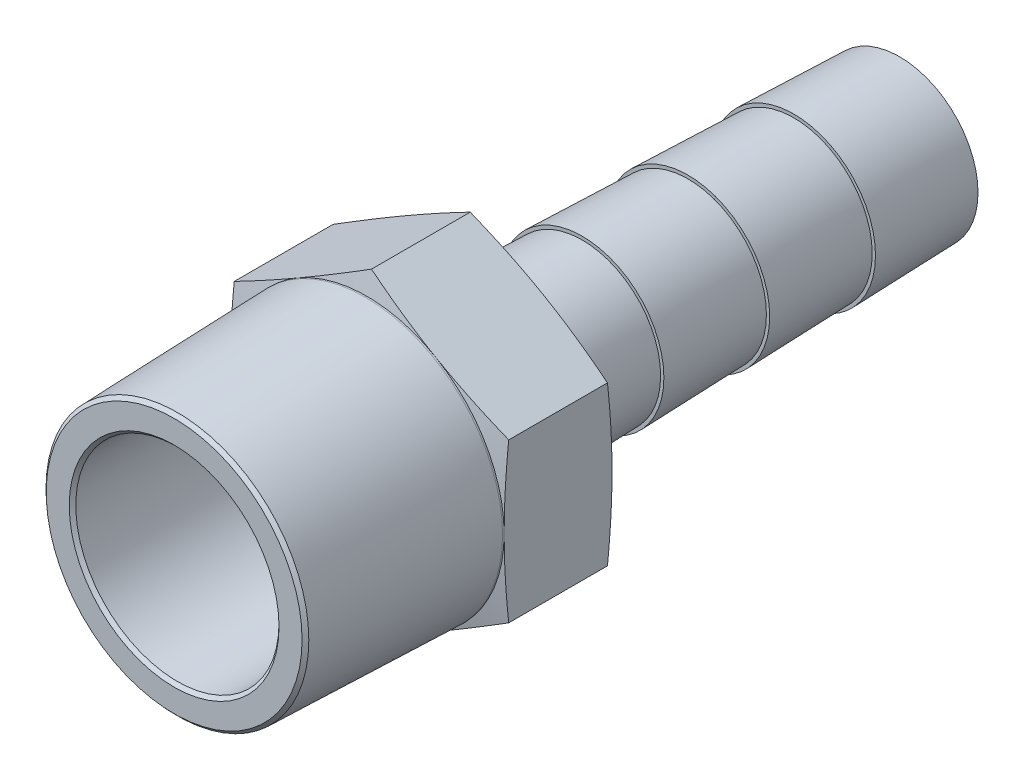
SolidWorks part; units mm, degrees
ref_plane "Front" through (0, 0, 0) normal (0, 0, 1) x (1, 0, 0)
ref_plane "Top" through (0, 0, 0) normal (0, 1, 0) x (1, 0, 0)
ref_plane "Right" through (0, 0, 0) normal (1, 0, 0) x (0, 0, -1)
sketch "PipeSketch" plane through (0, 0, 0) normal (0, 0, 1) x (1, 0, 0)
  circle A0 centre (0, 0) radius 10.668
  circle A1 centre (0, 0) radius 5.842
  dimension "OuterDiameter" = 21.336
  dimension "InnerDiameter" = 11.684
extrude "Extrusion" add sketch "PipeSketch" along normal blind 56.388
ref_plane "Plane5" through (0, 0, 33.02) normal (0, 0, -1) x (-1, 0, 0)
sketch "Sketch1" plane through (0, 0, 33.02) normal (0, 0, 1) x (1, 0, 0)
  line L1 (10.668, 6.1592) -> (0, 12.3183)
  line L2 (0, 12.3183) -> (-10.668, 6.1592)
  line L3 (-10.668, 6.1592) -> (-10.668, -6.1592)
  line L4 (-10.668, -6.1592) -> (0, -12.3183)
  line L5 (0, -12.3183) -> (10.668, -6.1592)
  line L6 (10.668, -6.1592) -> (10.668, 6.1592)
  circle A0 centre (0, 0) radius 10.668 construction
  circle A1 centre (0, 0) radius 5.842 construction
  circle A2 centre (0, 0) radius 5.842
  dimension "D1" = 21.336
extrude "Boss-Extrude1" add sketch "Sketch1" along normal blind 8.382
sketch "FilterSketch" plane through (0, 0, 0) normal (0, 0, 1) x (1, 0, 0)
  circle A0 centre (0, 0) radius 6.35
  dimension "NominalDiameter" = 12.7
sketch "Sketch9" plane through (0, 0, 56.388) normal (0, 0, 1) x (1, 0, 0)
  circle A0 centre (0, 0) radius 7.8994
  dimension "Thread end Dia" = 15.7988
extrude "Cut-Extrude1" cut sketch "Sketch9" against normal blind 14.986
sketch "Sketch7" plane through (0, 0, 0) normal (1, 0, 0) x (0, 0, -1)
  line L0 (-56.388, 10.668) -> (-56.388, 10.2062)
  line L1 (-56.388, 10.668) -> (-56.388, -10.668) construction
  line L2 (-56.388, 10.2062) -> (-41.529, 10.668)
  line L3 (-41.402, 10.668) -> (-56.388, 10.668) construction
  line L4 (-41.529, 10.668) -> (-56.388, 10.668)
  line L5 (0, 10.668) -> (-33.02, 10.668)
  line L6 (-33.02, 10.668) -> (-33.02, 6.35)
  line L7 (0, -10.668) -> (0, 10.668) construction
  line L8 (-33.02, 6.35) -> (-32.893, 6.35)
  line L9 (0, 0) -> (15.0254, 0) construction
  line L10 (-33.02, 6.1592) -> (-33.02, 9.2388) construction
  line L11 (-32.893, 6.35) -> (-24.6698, 6.096)
  line L12 (-24.6698, 6.096) -> (-24.6698, 6.35)
  line L13 (-24.6698, 6.35) -> (-16.4465, 6.096)
  line L14 (-16.4465, 6.096) -> (-16.4465, 6.35)
  line L15 (-16.4465, 6.35) -> (-8.2233, 6.096)
  line L16 (-8.2233, 6.096) -> (-8.2233, 6.35)
  line L17 (-8.2233, 6.35) -> (0, 6.096)
  line L19 (0, 6.096) -> (0, 10.668)
  dimension "D1" = 1.78
  dimension "Thread Length 1" = 14.859
  dimension "Hose dia" = 12.7
  dimension "D2" = 0.254
  dimension "Hose Length" = 32.893
  dimension "D3" = 8.2233
revolve "Cut-Revolve7" cut sketch "Sketch7" angle 360 about L9
sketch "Sketch4" plane through (0, 0, 0) normal (0, 1, 0) x (1, 0, 0)
  line L0 (-10.668, -41.402) -> (-19.558, -41.402)
  line L1 (-19.558, -41.402) -> (-19.558, -39.497)
  line L2 (-19.558, -39.497) -> (-10.668, -41.402)
  line L3 (-10.668, -33.02) -> (-19.558, -33.02)
  line L4 (-19.558, -33.02) -> (-19.558, -34.925)
  line L5 (-19.558, -34.925) -> (-10.668, -33.02)
  line L6 (0, 0) -> (0, -35.6608) construction
  dimension "D1" = 8.89
  dimension "D2" = 8.89
  dimension "D3" = 1.905
  dimension "D4" = 1.905
revolve "Cut-Revolve6" cut sketch "Sketch4" angle 360 about L6
chamfer "Chamfer1" distance 0.254 angle 45 2 edges at (10.2062, 0, 56.388) (7.8994, 0, 56.388) first distance on face at (10.668, 0, 41.529) first distance on face at (7.8994, 0, 56.388)
ref_plane "Plane6" through (0, 0, 41.529) normal (0, 0, 1) x (1, 0, 0)
ref_plane "Plane7" through (0, 0, 37.211) normal (0, 0, -1) x (-1, 0, 0)
sketch "Sketch5" plane through (0, 0, 41.529) normal (0, 0, 1) x (1, 0, 0)
  point P0 (0, 0)
sketch "Sketch6" plane through (0, 0, 33.02) normal (0, 0, 1) x (1, 0, 0)
  point P0 (0, 0)
sketch "Sketch8" plane through (0, 0, 37.211) normal (0, 0, 1) x (1, 0, 0)
  point P0 (0, 0)
other "CPoint1" parameters "Diameter"=12.7, "StubLength"=38.1
ref_axis "Axis1" through (0, 0, 51.529) along (0, 0, -1)
other "CPoint2" parameters "Diameter"=12.7, "StubLength"=38.1
ref_axis "Axis2" through (0, 0, 23.02) along (0, 0, 1)
other "RPoint1"
equation "\"L\"= \"Length@Extrusion\""
equation "\"D1@Sketch1\"= \"OuterDiameter@PipeSketch\""
equation "\"L2\"= 0.39"
equation "\"D3@Sketch7\"=\"Hose Length@Sketch7\"/4"
equation "\"D1@Plane7\"= \"Hex Length@Boss-Extrude1\" / 2"
equation "\"D3@Sketch4\"=\"D4@Sketch4\""
equation "\"D2@Sketch4\"=\"D1@Sketch4\""
